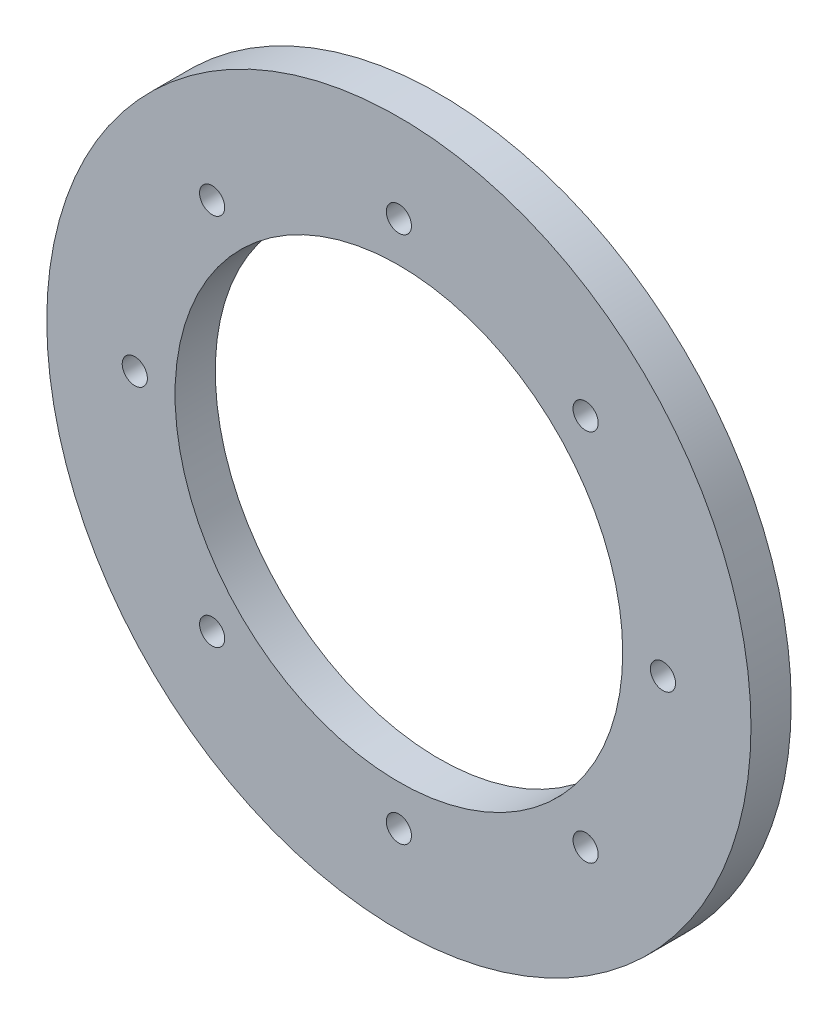
SolidWorks part; units mm, degrees
material "Thornel Mat VMA"
ref_plane "Front Plane" through (0, 0, 0) normal (0, 0, 1) x (1, 0, 0)
ref_plane "Top Plane" through (0, 0, 0) normal (0, 1, 0) x (1, 0, 0)
ref_plane "Right Plane" through (0, 0, 0) normal (1, 0, 0) x (0, 0, -1)
sketch "Sketch1" plane through (0, 0, 0) normal (0, 0, 1) x (1, 0, 0)
  circle A0 centre (0, 0) radius 44.5 construction
  circle A1 centre (0, 0) radius 44.5
  circle A2 centre (37.1231, -37.1231) radius 2.5 construction
  circle A3 centre (52.5, 0) radius 2.5 construction
  circle A4 centre (0, -52.5) radius 2.5 construction
  circle A5 centre (-37.1231, -37.1231) radius 2.5 construction
  circle A6 centre (-52.5, 0) radius 2.5 construction
  circle A7 centre (37.1231, 37.1231) radius 2.5 construction
  circle A8 centre (-37.1231, 37.1231) radius 2.5 construction
  circle A9 centre (0, 52.5) radius 2.5 construction
  circle A10 centre (37.1231, -37.1231) radius 2.5
  circle A11 centre (52.5, 0) radius 2.5
  circle A12 centre (0, -52.5) radius 2.5
  circle A13 centre (-37.1231, -37.1231) radius 2.5
  circle A14 centre (-52.5, 0) radius 2.5
  circle A15 centre (37.1231, 37.1231) radius 2.5
  circle A16 centre (-37.1231, 37.1231) radius 2.5
  circle A17 centre (0, 52.5) radius 2.5
  circle A18 centre (0, 0) radius 70
  dimension "D1" = 140
extrude "Boss-Extrude1" add sketch "Sketch1" along normal blind 8
